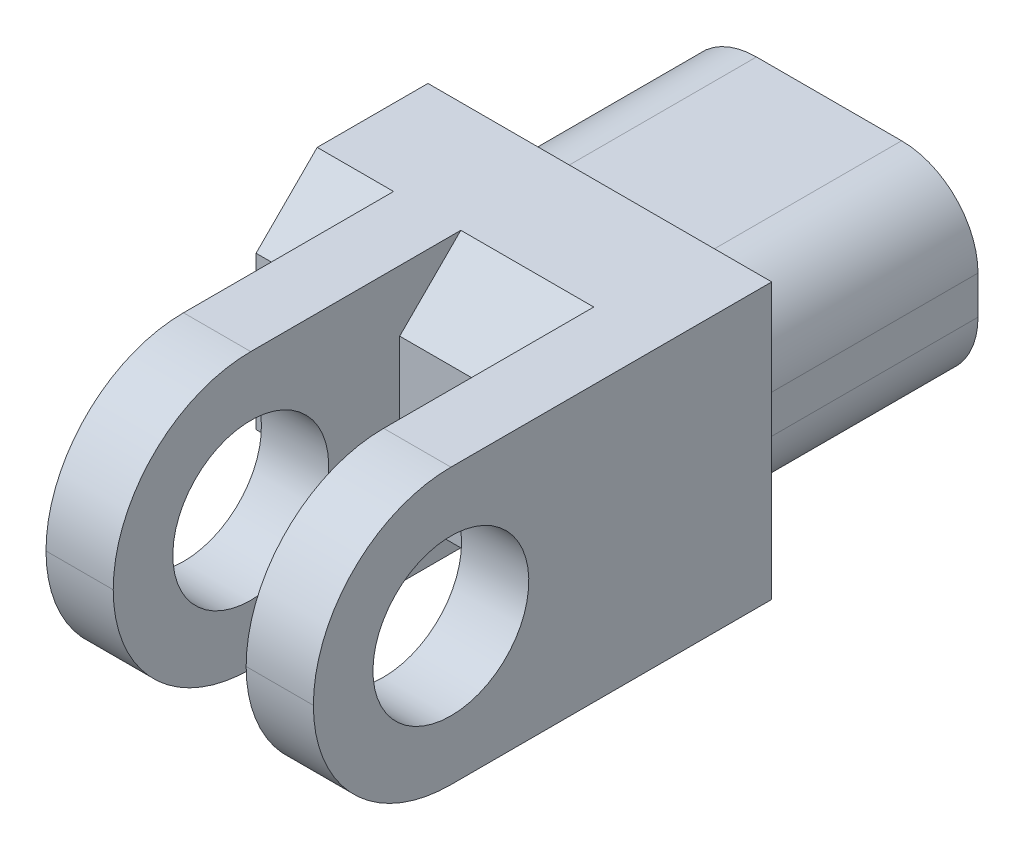
SolidWorks part; units mm, degrees
ref_plane "Plan de face" through (0, 0, 0) normal (0, 0, 1) x (1, 0, 0)
ref_plane "Plan de dessus" through (0, 0, 0) normal (0, 1, 0) x (1, 0, 0)
ref_plane "Plan de droite" through (0, 0, 0) normal (1, 0, 0) x (0, 0, -1)
sketch "Sketch2" plane through (0, 0, 0) normal (0, 0, 1) x (1, 0, 0)
  line L1 (12.3825, -7.9375) -> (-12.3825, -7.9375)
  line L2 (12.3825, -7.9375) -> (12.3825, 7.9375)
  line L3 (12.3825, 7.9375) -> (-12.3825, 7.9375)
  line L4 (-12.3825, -7.9375) -> (-12.3825, 7.9375)
  line L5 (12.3825, -7.9375) -> (-12.3825, 7.9375) construction
  line L6 (12.3825, 7.9375) -> (-12.3825, -7.9375) construction
  point P0 (0, 0)
  dimension "D1" = 24.765
  dimension "D2" = 15.875
extrude "Boss-Extrude1" add sketch "Sketch2" against normal blind 19.05
sketch "Sketch3" plane through (0, 0, 0) normal (0, 0, 1) x (1, 0, 0)
  line L1 (14.2875, -11.43) -> (-14.2875, -11.43)
  line L2 (14.2875, -11.43) -> (14.2875, 11.43)
  line L3 (14.2875, 11.43) -> (-14.2875, 11.43)
  line L4 (-14.2875, -11.43) -> (-14.2875, 11.43)
  line L5 (14.2875, -11.43) -> (-14.2875, 11.43) construction
  line L6 (14.2875, 11.43) -> (-14.2875, -11.43) construction
  point P0 (0, 0)
  dimension "D1" = 28.575
  dimension "D2" = 22.86
extrude "Boss-Extrude2" add sketch "Sketch3" along normal blind 38.1
sketch "Sketch4" plane through (0, -11.43, 0) normal (0, -1, 0) x (-1, 0, 0)
  line L0 (14.2875, -38.1) -> (-14.2875, -38.1) construction
  line L1 (14.2875, -38.1) -> (7.9375, -38.1)
  line L2 (14.2875, -38.1) -> (14.2875, -14.2875)
  line L3 (14.2875, -14.2875) -> (7.9375, -14.2875)
  line L4 (7.9375, -38.1) -> (7.9375, -14.2875)
  line L5 (2.3495, -38.1) -> (-8.6995, -38.1)
  line L6 (2.3495, -38.1) -> (2.3495, -14.2875)
  line L7 (2.3495, -14.2875) -> (-8.6995, -14.2875)
  line L8 (-8.6995, -38.1) -> (-8.6995, -14.2875)
  line L9 (-14.2875, -38.1) -> (-14.2875, 0) construction
  dimension "D1" = 23.8125
  dimension "D2" = 23.8125
  dimension "D3" = 6.35
  dimension "D4" = 5.588
  dimension "D5" = 5.588
extrude "Cut-Extrude1" cut sketch "Sketch4" against normal through all
fillet "Fillet5" radius 11.43 4 edges at (-5.1435, -11.43, 38.1) (-5.1435, 11.43, 38.1) (11.4935, 11.43, 38.1) (11.4935, -11.43, 38.1)
sketch "Sketch7" plane through (-7.9375, 0, 0) normal (-1, 0, 0) x (0, 0, 1)
  circle A1 centre (26.67, 0) radius 6.477
  dimension "D1" = 12.954
extrude "Cut-Extrude3" cut sketch "Sketch7" against normal through all
fillet "Fillet3" radius 6.35 4 edges at (-12.3825, -7.9375, -9.525) (-12.3825, 7.9375, -9.525) (12.3825, -7.9375, -9.525) (12.3825, 7.9375, -9.525)
chamfer "Chamfer1" distance 5.08 angle 45 4 edges at (3.175, -11.43, 14.2875) (-11.1125, -11.43, 14.2875) (-11.1125, 11.43, 14.2875) (3.175, 11.43, 14.2875)
